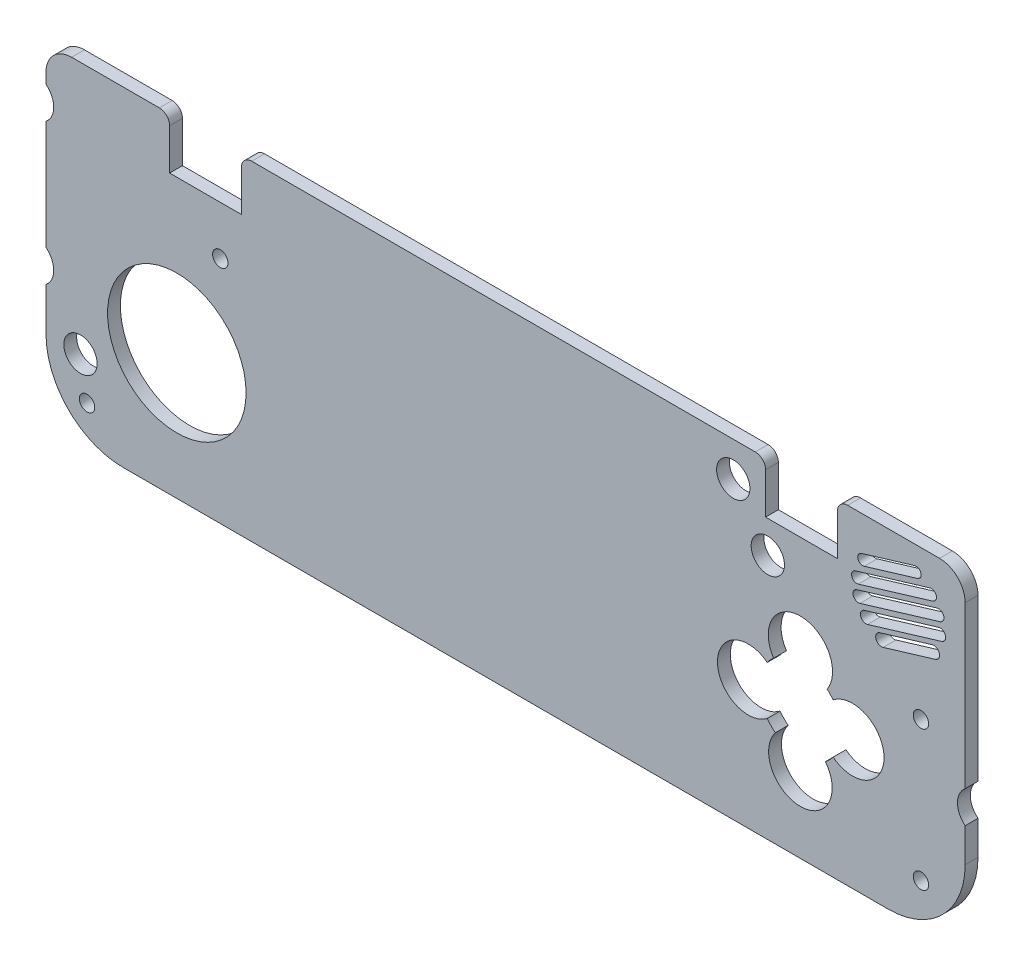
SolidWorks part; units mm, degrees
ref_plane "Plan de face" through (0, 0, 0) normal (0, 0, 1) x (1, 0, 0)
ref_plane "Plan de dessus" through (0, 0, 0) normal (0, 1, 0) x (1, 0, 0)
ref_plane "Plan de droite" through (0, 0, 0) normal (1, 0, 0) x (0, 0, -1)
sketch "Esquisse1" plane through (0, 0, 0) normal (0, 0, 1) x (1, 0, 0)
  line L1 (-89.2039, 33.3448) -> (79.9661, 33.3448)
  line L2 (-94.2039, 28.3448) -> (-94.2039, -15.8852)
  line L3 (-79.2039, -30.8852) -> (69.9661, -30.8852)
  line L4 (84.9661, 28.3448) -> (84.9661, -15.8852)
  arc A0 (-89.2039, 33.3448) -> (-94.2039, 28.3448) centre (-89.2039, 28.3448) ccw
  arc A1 (79.9661, 33.3448) -> (84.9661, 28.3448) centre (79.9661, 28.3448) cw
  arc A2 (69.9661, -30.8852) -> (84.9661, -15.8852) centre (69.9661, -15.8852) ccw
  arc A3 (-94.2039, -15.8852) -> (-79.2039, -30.8852) centre (-79.2039, -15.8852) ccw
  point P6 (-94.2039, 33.3448)
  point P9 (84.9661, 33.3448)
  point P12 (84.9661, -30.8852)
  dimension "D3" = 5
  dimension "D4" = 5
  dimension "D5" = 15
  dimension "D6" = 15
  dimension "D1" = 179.17
  dimension "D2" = 64.23
extrude "Boss.-Extru.1" add sketch "Esquisse1" along normal blind 2.5 contours L1 A1 L4 A2 L3 A3 L2 A0
sketch "12x12 Button" plane through (0, 0, 2.5) normal (0, 0, 1) x (1, 0, 0)
  line L0 (84.9661, 28.3448) -> (84.9661, -15.8852) construction
  line L1 (-79.2039, -30.8852) -> (69.9661, -30.8852) construction
  line L2 (52.8461, 3.7748) -> (52.8461, -15.9152)
  line L3 (42.6861, -5.7552) -> (63.0061, -5.7552)
  circle A0 centre (42.6861, -5.7552) radius 5.9988
  circle A1 centre (52.8461, 3.7748) radius 6.2634
  circle A2 centre (52.8461, -15.9152) radius 6.1927
  circle A3 centre (63.0061, -5.7552) radius 6.14
  arc A5 (46.3825, -1.0306) -> (47.6252, 0.3146) centre (52.8461, -5.7552) cw
  arc A6 (59.2204, -0.9212) -> (58.0635, 0.3093) centre (52.8461, -5.7552) ccw
  arc A7 (46.3874, -10.476) -> (47.9701, -12.0975) centre (52.8461, -5.7552) ccw
  arc A10 (57.722, -12.0975) -> (59.2204, -10.5893) centre (52.8461, -5.7552) ccw
  dimension "D1" = 21.96
  dimension "D2" = 32.12
  dimension "D3" = 42.28
  dimension "D4" = 32.12
  dimension "D5" = 14.97
  dimension "D6" = 34.66
  dimension "D7" = 25.13
  dimension "D8" = 25.13
extrude "Enlèv. mat.-Extru.14" cut sketch "12x12 Button" against normal blind 10 contours A0 | A1 | A5 A0 L3 L2 A1 | A0 A7 A2 L2 L3 | A2 A10 A3 L3 L2 | A3 A6 A1 L2 L3 | A2 | A3 region at (55.6454, -3.3252, 2.5) region at (49.9662, -3.3183, 2.5) region at (49.9669, -1.5874, 2.5) region at (55.6071, -8.4886, 2.5) region at (50.0167, -8.4832, 2.5) region at (55.4812, -10.5053, 2.5) region at (47.9275, -8.306, 2.5) region at (57.6421, -3.1428, 2.5)
sketch "Joystick" plane through (0, 0, 2.5) normal (0, 0, 1) x (1, 0, 0)
  line L0 (-79.2039, -30.8852) -> (69.9661, -30.8852) construction
  line L1 (-94.2039, 28.3448) -> (-94.2039, -15.8852) construction
  circle A0 centre (-68.7039, -6.3252) radius 13.5
  dimension "D1" = 24.56
  dimension "D2" = 25.5
extrude "Enlèv. mat.-Extru.2" cut sketch "Joystick" against normal blind 2.5
sketch "Esquisse2" plane through (0, 0, 2.5) normal (0, 0, 1) x (1, 0, 0)
  line L0 (-89.2039, 33.3448) -> (79.9661, 33.3448) construction
  line L1 (46.0561, 33.3448) -> (60.0561, 33.3448)
  line L2 (46.0561, 33.3448) -> (46.0561, 23.3448)
  line L3 (46.0561, 23.3448) -> (60.0561, 23.3448)
  line L4 (60.0561, 33.3448) -> (60.0561, 23.3448)
  line L5 (84.9661, 28.3448) -> (84.9661, -15.8852) construction
  dimension "D1" = 24.91
  dimension "D2" = 14
extrude "Enlèv. mat.-Extru.3" cut sketch "Esquisse2" against normal blind 10
fillet "Congé1" radius 2 1 edges at (46.0561, 33.3448, 1.25)
fillet "Congé2" radius 2 1 edges at (60.0561, 33.3448, 1.25)
sketch "Esquisse3" plane through (0, 0, 2.5) normal (0, 0, 1) x (1, 0, 0)
  line L0 (-89.2039, 33.3448) -> (44.0561, 33.3448) construction
  line L1 (-70.1039, 33.3448) -> (-56.1039, 33.3448)
  line L2 (-70.1039, 33.3448) -> (-70.1039, 23.3448)
  line L3 (-70.1039, 23.3448) -> (-56.1039, 23.3448)
  line L4 (-56.1039, 33.3448) -> (-56.1039, 23.3448)
  line L5 (-94.2039, 28.3448) -> (-94.2039, -15.8852) construction
  dimension "D1" = 24.1
  dimension "D2" = 10
  dimension "D3" = 14
extrude "Enlèv. mat.-Extru.4" cut sketch "Esquisse3" against normal blind 10 contours L2 L1 L4 L3
fillet "Congé3" radius 2 1 edges at (-70.1039, 33.3448, 1.25)
fillet "Congé4" radius 2 1 edges at (-56.1039, 33.3448, 1.25)
sketch "Esquisse4" plane through (0, 0, 2.5) normal (0, 0, 1) x (1, 0, 0)
  line L0 (84.9661, 28.3448) -> (84.9661, -15.8852) construction
  line L1 (64.1511, 18.9874) -> (79.781, 23.7022) construction
  line L2 (62.0561, 33.3448) -> (79.9661, 33.3448) construction
  line L3 (63.8482, 19.9918) -> (79.478, 24.7066)
  line L4 (64.4541, 17.983) -> (80.084, 22.6978)
  line L5 (63.8337, 22.048) -> (78.3531, 26.4278) construction
  line L6 (63.5398, 23.0223) -> (78.0592, 27.4021)
  line L7 (64.1276, 21.0736) -> (78.647, 25.4535)
  line L8 (65.0061, 25.6097) -> (75.4066, 28.7471) construction
  line L9 (64.7213, 26.554) -> (75.1217, 29.6914)
  line L10 (65.291, 24.6654) -> (75.6914, 27.8027)
  line L11 (65.627, 16.2022) -> (80.0915, 20.5654) construction
  line L12 (65.3147, 17.2374) -> (79.7793, 21.6007)
  line L13 (65.9393, 15.1669) -> (80.4038, 19.5302)
  line L14 (68.6474, 13.8871) -> (78.8552, 16.9663) construction
  line L15 (68.3228, 14.9633) -> (78.5305, 18.0425)
  line L16 (68.9721, 12.8109) -> (79.1798, 15.8901)
  circle A0 centre (71.9661, 21.3448) radius 10
  circle A1 centre (71.9661, 21.3448) radius 8.1628
  arc A2 (63.8482, 19.9918) -> (64.4541, 17.983) centre (64.1511, 18.9874) ccw
  arc A3 (80.084, 22.6978) -> (79.478, 24.7066) centre (79.781, 23.7022) ccw
  arc A4 (63.5398, 23.0223) -> (64.1276, 21.0736) centre (63.8337, 22.048) ccw
  arc A5 (78.647, 25.4535) -> (78.0592, 27.4021) centre (78.3531, 26.4278) ccw
  arc A6 (64.7213, 26.554) -> (65.291, 24.6654) centre (65.0061, 25.6097) ccw
  arc A7 (75.6914, 27.8027) -> (75.1217, 29.6914) centre (75.4066, 28.7471) ccw
  arc A8 (65.3147, 17.2374) -> (65.9393, 15.1669) centre (65.627, 16.2022) ccw
  arc A9 (80.4038, 19.5302) -> (79.7793, 21.6007) centre (80.0915, 20.5654) ccw
  arc A10 (68.3228, 14.9633) -> (68.9721, 12.8109) centre (68.6474, 13.8871) ccw
  arc A11 (79.1798, 15.8901) -> (78.5305, 18.0425) centre (78.8552, 16.9663) ccw
  point P9 (71.9661, 21.3448)
  point P16 (71.0934, 24.2379)
  point P25 (70.2064, 27.1784)
  point P36 (72.8593, 18.3838)
  point P47 (73.7513, 15.4267)
  dimension "D1" = 13
  dimension "D2" = 12
  dimension "D4" = 0
  dimension "D5" = 1.0673
  dimension "D6" = 360
  dimension "D7" = 360
  dimension "D8" = 0.8833
extrude "Enlèv. mat.-Extru.8" cut sketch "Esquisse4" against normal blind 10 contours L4 A1 L3 | L3 A2 A0 L4 A1 | L6 A4 A0 A1 | L9 A6 A0 A1 | L10 A7 A1 L9 A6 | A1 A9 L12 A8 L13 | A1 A8 A0 L13 | A1 A10 A0 L16 | A1 A11 L15 A10 L16 | L16 A11 A0 A1 | A0 A9 A1 L13 | A0 A3 L3 A1 L4 | A0 A5 L6 A1 | L7 A5 A1 L6 A4 | A0 A7 L9 A1 region at (63.7367, 18.8624, 2.5) region at (71.9661, 21.3448, 2.5) region at (80.1954, 23.8272, 2.5) region at (63.4195, 22.0941, 2.5) region at (71.0986, 24.2207, 2.5) region at (78.6726, 26.6952, 2.5) region at (72.8532, 18.4038, 2.5) region at (65.2917, 15.9147, 2.5) region at (80.5298, 20.5113, 2.5) region at (64.7542, 25.9173, 2.5) region at (70.2242, 27.1192, 2.5) region at (75.4463, 29.1426, 2.5) region at (73.7264, 15.5093, 2.5) region at (68.6334, 13.4338, 2.5) region at (79.1175, 16.5964, 2.5)
sketch "Esquisse5" plane through (0, 0, 2.5) normal (0, 0, 1) x (1, 0, 0)
  line L0 (84.9661, 28.3448) -> (84.9661, -15.8852) construction
  line L1 (-79.2039, -30.8852) -> (69.9661, -30.8852) construction
  line L2 (-94.2039, 28.3448) -> (-94.2039, -15.8852) construction
  line L7 (62.0561, 33.3448) -> (79.9661, 33.3448) construction
  line L8 (-54.1039, 33.3448) -> (44.0561, 33.3448) construction
  circle A0 centre (76.3461, -22.8852) radius 1.5
  circle A1 centre (-86.2039, -23.5352) radius 1.5
  circle A2 centre (76.3461, 4.3448) radius 1.5
  circle A3 centre (-60.2339, 13.8348) radius 1.5
  circle A4 centre (-87.4839, -15.9152) radius 3.25
  circle A5 centre (39.7561, 26.6248) radius 3.25
  circle A6 centre (46.4961, 17.1048) radius 3.25
  dimension "D1" = 8.62
  dimension "D3" = 7.35
  dimension "D5" = 8.62
  dimension "D7" = 19.51
  dimension "D9" = 6.72
  dimension "D11" = 6.72
  dimension "D13" = 38.47
  dimension "D2" = 8
  dimension "D4" = 8
  dimension "D6" = 29
  dimension "D8" = 33.97
  dimension "D10" = 14.97
  dimension "D12" = 45.21
  dimension "D14" = 16.24
extrude "Enlèv. mat.-Extru.9" cut sketch "Esquisse5" against normal blind 10
sketch "Esquisse6" plane through (0, 0, 2.5) normal (0, 0, 1) x (1, 0, 0)
  line L0 (-76.1808, -30.8852) -> (-76.1808, -4.3852)
  line L1 (-79.2039, -30.8852) -> (69.9661, -30.8852) construction
  line L2 (-76.1808, -4.3852) -> (-94.2039, -4.3852)
  line L3 (-94.2039, 28.3448) -> (-94.2039, -15.8852) construction
  line L4 (-94.2039, -4.3852) -> (-99.2039, -4.3852)
  line L5 (-80.6539, 33.3448) -> (-80.6539, 23.1548)
  line L6 (-89.2039, 33.3448) -> (-72.1039, 33.3448) construction
  line L7 (-80.6539, 23.1548) -> (-94.2039, 23.1548)
  line L8 (-94.2039, 23.1548) -> (-99.2039, 23.1548)
  line L9 (68.4263, -30.8852) -> (68.4263, -6.1652)
  line L10 (68.4263, -6.1652) -> (84.9661, -6.1652)
  line L11 (84.9661, 28.3448) -> (84.9661, -15.8852) construction
  line L12 (84.9661, -6.1652) -> (89.9661, -6.1652)
  circle A0 centre (-96.7039, -4.3852) radius 4
  circle A1 centre (-96.7039, 23.1548) radius 4
  circle A2 centre (87.4661, -6.1652) radius 4
extrude "Enlèv. mat.-Extru.15" cut sketch "Esquisse6" against normal blind 10
